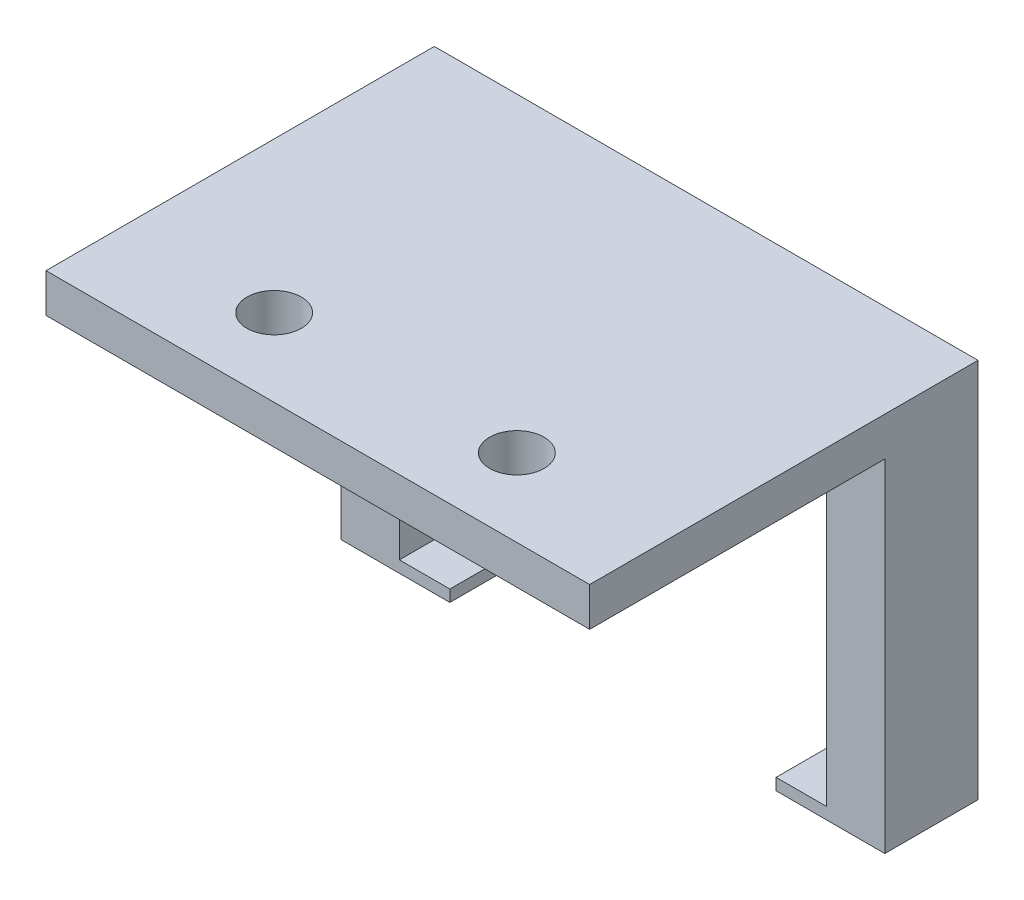
SolidWorks part; units mm, degrees
material "Custom Plastic"
ref_plane "Front Plane" through (0, 0, 0) normal (0, 0, 1) x (1, 0, 0)
ref_plane "Top Plane" through (0, 0, 0) normal (0, 1, 0) x (1, 0, 0)
ref_plane "Right Plane" through (0, 0, 0) normal (1, 0, 0) x (0, 0, -1)
sketch "Sketch3" plane through (0, 0, 0) normal (0, 1, 0) x (1, 0, 0)
  line L1 (-11.5173, 12.4673) -> (24.0427, 12.4673)
  line L2 (-11.5173, 12.4673) -> (-11.5173, -12.9327)
  line L3 (-11.5173, -12.9327) -> (24.0427, -12.9327)
  line L4 (24.0427, 12.4673) -> (24.0427, -12.9327)
  circle A0 centre (-1.6748, -7.8527) radius 1.778
  circle A2 centre (14.2002, -7.8527) radius 1.778
  dimension "D2" = 3.556
  dimension "D3" = 3.556
  dimension "D1" = 25.4
  dimension "1" = 35.56
  dimension "D4" = 15.875
  dimension "D5" = 9.8425
  dimension "D6" = 20.32
extrude "Boss-Extrude3" add sketch "Sketch3" along normal blind 2.54
sketch "Sketch4" plane through (0, 0, 0) normal (0, -1, 0) x (1, 0, 0)
  line L0 (-11.5173, -12.4673) -> (-11.5173, 12.9327) construction
  line L1 (-11.5173, -1.2913) -> (-7.7073, -1.2913)
  line L2 (-11.5173, -1.2913) -> (-11.5173, -12.4673)
  line L3 (-11.5173, -12.4673) -> (-7.7073, -12.4673)
  line L4 (-7.7073, -1.2913) -> (-7.7073, -12.4673)
  line L5 (24.0427, -12.4673) -> (-11.5173, -12.4673) construction
  line L6 (-11.5173, 12.9327) -> (24.0427, 12.9327) construction
  line L7 (24.0427, 12.9327) -> (24.0427, -12.4673) construction
  line L8 (24.0427, -1.2913) -> (20.2327, -1.2913)
  line L9 (24.0427, -1.2913) -> (24.0427, -12.4673)
  line L10 (24.0427, -12.4673) -> (20.2327, -12.4673)
  line L11 (20.2327, -1.2913) -> (20.2327, -12.4673)
  dimension "D1" = 14.224
  dimension "D2" = 3.81
  dimension "D3" = 14.224
  dimension "D4" = 3.81
extrude "Boss-Extrude4" add sketch "Sketch4" along normal blind 22.352
sketch "Sketch5" plane through (-7.7073, 0, 0) normal (1, 0, 0) x (0, 0, -1)
  line L0 (1.2913, -22.352) -> (1.2913, 0) construction
  line L1 (1.2913, -21.59) -> (12.4673, -21.59)
  line L2 (1.2913, -21.59) -> (1.2913, -22.352)
  line L3 (1.2913, -22.352) -> (12.4673, -22.352)
  line L4 (12.4673, -21.59) -> (12.4673, -22.352)
  dimension "D1" = 0.762
extrude "Boss-Extrude5" add sketch "Sketch5" along normal blind 3.302
sketch "Sketch6" plane through (20.2327, 0, 0) normal (-1, 0, 0) x (0, 0, 1)
  line L0 (-12.4673, 2.54) -> (-12.4673, -22.352) construction
  line L1 (-12.4673, -21.59) -> (-1.2913, -21.59)
  line L2 (-12.4673, -21.59) -> (-12.4673, -22.352)
  line L3 (-12.4673, -22.352) -> (-1.2913, -22.352)
  line L4 (-1.2913, -21.59) -> (-1.2913, -22.352)
  dimension "D1" = 0.762
extrude "Boss-Extrude6" add sketch "Sketch6" along normal blind 3.302
sketch "Sketch7" plane through (0, 0, -1.2913) normal (0, 0, 1) x (1, 0, 0)
  line L1 (-11.5173, 0) -> (24.0427, 0)
  line L2 (-11.5173, 0) -> (-11.5173, -22.352)
  line L3 (-11.5173, -22.352) -> (24.0427, -22.352)
  line L4 (24.0427, 0) -> (24.0427, -22.352)
extrude "Cut-Extrude1" cut sketch "Sketch7" against normal blind 5.08
